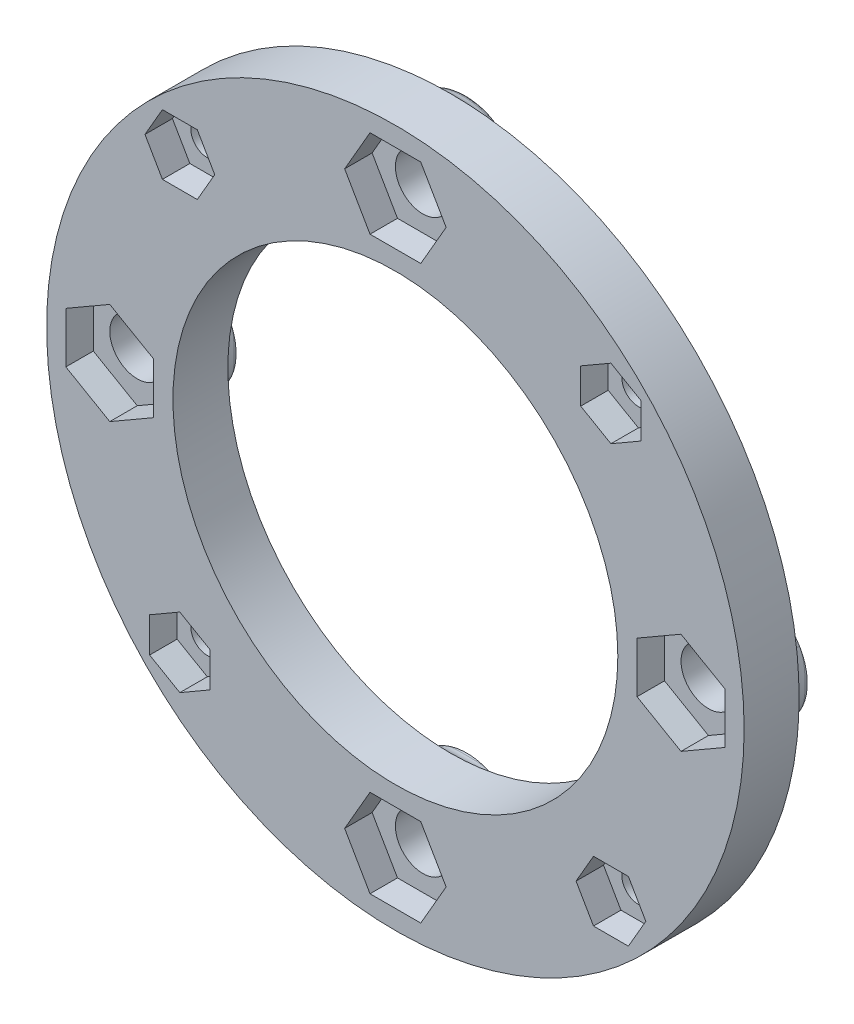
SolidWorks part; units mm, degrees
material "PLA"
ref_plane "Front Plane" through (0, 0, 0) normal (0, 0, 1) x (1, 0, 0)
ref_plane "Top Plane" through (0, 0, 0) normal (0, 1, 0) x (1, 0, 0)
ref_plane "Right Plane" through (0, 0, 0) normal (1, 0, 0) x (0, 0, -1)
sketch "Sketch2" plane through (0, 0, 0) normal (0, 0, 1) x (1, 0, 0)
  line L0 (0, 26) -> (0, 0) construction
  line L1 (0, 0) -> (19.6222, 19.6222) construction
  circle A0 centre (0, 0) radius 31.75
  circle A2 centre (0, 0) radius 26 construction
  circle A3 centre (0, 26) radius 2.5
  circle A4 centre (0, 0) radius 27.75 construction
  circle A5 centre (26, 0) radius 2.5
  circle A8 centre (19.6222, 19.6222) radius 1.5
  circle A9 centre (19.6222, -19.6222) radius 1.5
  circle A11 centre (0, 0) radius 14 construction
  circle A14 centre (0, 26) radius 4.25 construction
  circle A15 centre (0, 0) radius 21.75 construction
  circle A16 centre (0, -26) radius 2.5
  circle A19 centre (-19.6222, -19.6222) radius 1.5
  circle A20 centre (0, 0) radius 30.25 construction
  circle A23 centre (0, 0) radius 20.25
  circle A31 centre (-26, 0) radius 2.5
  circle A33 centre (-19.6222, 19.6222) radius 1.5
  point P17 (0, 0)
  point P24 (0, 0)
  dimension "D2" = 52
  dimension "D4" = 5
  dimension "D7" = 3
  dimension "D3" = 28
  dimension "D10" = 8.5
  dimension "D5" = 4
  dimension "D11" = 45
  dimension "D12" = 1.5
  dimension "D9" = 1.5
  dimension "D6" = 4
  dimension "D8" = 4
extrude "Boss-Extrude1" add sketch "Sketch2" along normal blind 5
sketch "Sketch3" plane through (0, 0, 5) normal (0, 0, 1) x (1, 0, 0)
  line L0 (0, 26) -> (0, 0) construction
  line L13 (-4.6188, 26) -> (-2.3094, 22)
  line L14 (-2.3094, 22) -> (2.3094, 22)
  line L15 (2.3094, 22) -> (4.6188, 26)
  line L16 (4.6188, 26) -> (2.3094, 30)
  line L17 (2.3094, 30) -> (-2.3094, 30)
  line L18 (-2.3094, 30) -> (-4.6188, 26)
  line L20 (19.6222, 16.4468) -> (22.3722, 18.0345)
  line L21 (22.3722, 18.0345) -> (22.3722, 21.2099)
  line L22 (22.3722, 21.2099) -> (19.6222, 22.7976)
  line L23 (19.6222, 22.7976) -> (16.8722, 21.2099)
  line L24 (16.8722, 21.2099) -> (16.8722, 18.0345)
  line L25 (16.8722, 18.0345) -> (19.6222, 16.4468)
  circle A0 centre (0, 26) radius 4 construction
  circle A1 centre (19.6222, 19.6222) radius 2.75 construction
  dimension "D1" = 8
  dimension "D2" = 5.5
extrude "Cut-Extrude1" cut sketch "Sketch3" against normal blind 2.5
pattern_circular "CirPattern1" count 4 over 360 about axis through (0, 0, 5) along (0, 0, -1) of "Cut-Extrude1" reverse direction yes
sketch "Sketch4" plane through (0, 0, 0) normal (0, 0, -1) x (-1, 0, 0)
  circle A0 centre (0, 26) radius 4
  circle A1 centre (0, 26) radius 5
  dimension "D1" = 8
extrude "Boss-Extrude2" add sketch "Sketch4" along normal blind 1.5
fillet "Fillet1" radius 1.5 1 edges at (5, 26, 0)
fillet "Fillet2" radius 0.5 4 edges at (0, 31, -1.5) (0, 21, -1.5) (4.9914, 25.7067, -1.5) (-4.9914, 25.7067, -1.5)
chamfer "Chamfer1" distance 0.25 angle 45 1 edges at (-4, 26, -1.5)
pattern_circular "CirPattern2" count 4 over 360 about axis through (0, 0, 5) along (0, 0, -1) of "Fillet1", "Boss-Extrude2", "Chamfer1" reverse direction yes
equation "\"module\" = 0.5"
equation "\"pressure_angle\" = 20.0"
equation "\"h_a\" = 0.5"
equation "\"h_f\" = 0.625"
equation "\"clr_tip_root\" = 0.125"
equation "\"bearing_ID\" = 60"
equation "\"bearing_OD\" = 78"
equation "\"bearing_height\" = 10"
equation "\"clearance_planet\" = 1.5"
equation "\"case_dist\" = 6.5"
equation "\"Motor_case_OD_max\" = 111.3"
equation "\"case_mounting_PCD\" = 103.8"
equation "\"bearing mount thickness\" = 8"
equation "\"case_mounting_hole_dia\" = 3"
equation "\"output_mounting_PCD\" = 86"
equation "\"output_mounting_hole_dia\" = 4"
equation "\"clearance_case_mount_holes_shell_thickness\" = 1"
equation "\"motor_case_OD_base\" = 101.8"
equation "\"sec_carrier_thickness\" = 5"
equation "\"sun_coupler_hub_thickness\" = 4"
equation "\"clearance_sun_coupler_sec_carrier\" = 1.5"
equation "\"clearance_motor_and_case\" = 5"
equation "\"motor_OD\" = 86.8"
equation "\"Motor_case_thickness\" = 2.5"
equation "\"Motor_case_ID\" = 96.8"
equation "\"case_mounting_hole_shift\" = 1.0"
equation "\"output_mounting_nut_wrench_size\" = 7"
equation "\"output_mounting_nut_thickness\" = 3.2"
equation "\"case_mounting_hole_allen_socket_dia\" = 5.5"
equation "\"output_mounting_nut_depth\" = 3"
equation "\"case_mounting_bolt_depth\" = 4.5"
equation "\"Ns\" = 56"
equation "\"Np_b\" = 48"
equation "\"ring_radial_thickness\" = 5"
equation "\"ring_to_chamfer_clearance\" = 1.5"
equation "\"Motor_case_OD_base_to_chamfer\" = 5"
equation "\"pattern_offset_from_motor_case_OD_base\" = 3"
equation "\"pattern_bulge_dia\" = 3"
equation "\"pattern_num_bulge\" = 18"
equation "\"pattern_depth\" = 2"
equation "\"motor_height\" = 26.5"
equation "\"case_mounting_wrench_size\" = 5.5"
equation "\"case_mounting_nut_clearance\" = 2"
equation "\"base_plate_thickness\" = 4"
equation "\"case_mounting_nut_thickness\" = 2.4"
equation "\"case_mounting_surface_height\" = 4"
equation "\"motor_mount_hole_PCD\" = 32"
equation "\"motor_mount_hole_dia\" = 4"
equation "\"motor_mount_hole_num\" = 4"
equation "\"central_hole_offset_from_motor_mount_PCD\" = 5"
equation "\"wire_slot_dist_from_center\" = 38"
equation "\"wire_slot_length\" = 10"
equation "\"wire_slot_radius\" = 2.5"
equation "\"driver_upper_holes_dist_from_center\" = 29"
equation "\"driver_lower_holes_dist_from_center\" = 13"
equation "\"driver_side_holes_dist_from_center\" = 22.5"
equation "\"driver_mount_holes_dia\" = 3"
equation "\"driver_mount_inserts_OD\" = 4.8"
equation "\"driver_mount_thickness\" = 1.5"
equation "\"driver_mount_height\" = 6"
equation "\"air_flow_hole_offset\" = 3"
equation "\"num_planet\" = 4"
equation "\"planet_pin_bolt_dia\" = 5"
equation "\"planet_pin_socket_head_dia\" = 8.5"
equation "\"carrier_PCD\" = 52.0"
equation "\"D2@Sketch2\"=\"carrier_PCD\""
equation "\"D4@Sketch2\"=\"planet_pin_bolt_dia\""
equation "\"D6@Sketch2\"=\"num_planet\""
equation "\"D8@Sketch2\"=\"num_planet\""
equation "\"D1@CirPattern1\"=\"num_planet\""
equation "\"planet_shaft_dia\" = 8"
equation "\"planet_shaft_step_offset\" = 1"
equation "\"carrier_trapezoidal_support_sun_offset\" = 5"
equation "\"carrier_trapezoidal_support_hole_PCD_offset_bearing_ID\" = 4"
equation "\"carrier_trapezoidal_support_hole_dia\" = 3"
equation "\"carrier_trapezoidal_support_hole_socket_head_dia\" = 5.5"
equation "\"carrier_bearing_step_width\" = 1.5"
equation "\"standard_clearance_1_5mm\" = 1.5"
equation "\"standard_fillet_1_5mm\" = 1.5"
equation "\"sun_shaft_bearing_OD\" = 16"
equation "\"sun_shaft_bearing_width\" = 5"
equation "\"standard_bearing_insertion_chamfer\" = 0.5"
equation "\"D7@Sketch2\"=\"carrier_trapezoidal_support_hole_dia\""
equation "\"D3@Sketch2\"=\"Ns\"*\"module\""
equation "\"carrier_trapezoidal_support_hole_wrench_size\" = 5.5"
equation "\"planet_pin_bolt_wrench_size\" = 8"
equation "\"D1@Boss-Extrude1\"=\"sec_carrier_thickness\""
equation "\"D1@Cut-Extrude1\"=\"sec_carrier_thickness\"/2"
equation "\"D1@Sketch4\"=\"planet_shaft_dia\""
equation "\"D2@Sketch4\"=\"planet_shaft_step_offset\""
equation "\"D1@Boss-Extrude2\"=\"clearance_planet\""
equation "\"D1@Fillet1\"=\"standard_fillet_1_5mm\""
equation "\"D1@Chamfer1\"=\"standard_bearing_insertion_chamfer\"/2"
equation "\"D1@Fillet2\"=\"standard_fillet_1_5mm\"/3"
equation "\"D1@CirPattern2\"=\"num_planet\""
equation "\"D10@Sketch2\"= \"planet_pin_socket_head_dia\""
equation "\"D1@Sketch3\"=\"planet_pin_bolt_wrench_size\""
equation "\"D11@Sketch2\"=180/\"num_planet\""
equation "\"D2@Sketch3\"=\"carrier_trapezoidal_support_hole_wrench_size\""
equation "\"pressure angle\" = 20.0"
equation "\"h_b\" = 0.625"
equation "\"dp_s\" = 28.0"
equation "\"db_s\" = 26.311393382005434"
equation "\"fw_s_calc\" = 2.7970255760332914"
equation "\"alpha_s\" = 0.8539582918412485"
equation "\"beta_s\" = 1.5063691306032174"
equation "\"dp_p_b\" = 24.0"
equation "\"db_p_b\" = 22.552622898861802"
equation "\"fw_p_s\" = 15.90536252346366"
equation "\"alpha_p_b\" = 0.8539582918412414"
equation "\"beta_p_b\" = 2.042083416317517"
equation "\"planet_bearing_OD\" = 12"
equation "\"planet_bearing_width\" = 3.5"
equation "\"planet_bore\" = 10"
equation "\"motor_output_hole_PCD\" = 23"
equation "\"motor_output_hole_dia\" = 4"
equation "\"motor_output_hole_num\" = 4"
equation "\"sun_shaft_bearing_ID\" = 8"
equation "\"sun_hub_dia\" = 30.0"
equation "\"sun_central_bolt_dia\" = 5"
equation "\"sun_central_bolt_socket_head_dia\" = 8.5"
equation "\"fw_s_used\" = 33.32338113475014"
equation "\"motor_output_hole_CSK_OD\" = 8"
equation "\"motor_output_hole_CSK_head_height\" = 2.0"
equation "\"bearing_retainer_thickness\" = 2"
equation "\"Np_s\" = 28"
equation "\"fw_p_b\" = 9.918018611286483"
equation "\"dp_p_s\" = 14.0"
equation "\"db_p_s\" = 13.155696691002717"
equation "\"alpha_p_s\" = 0.8539582918412485"
equation "\"beta_p_s\" = 4.720654844888932"
equation "\"Nr_b\" = 152"
equation "\"dp_r_b\" = 76.0"
equation "\"db_r_b\" = 71.41663917972905"
equation "\"fw_r_b\" = 9.918018611286483"
equation "\"alpha_r_b\" = 0.8539582918412236"
equation "\"beta_r_b\" = 2.8921271099982366"
equation "\"ring_OD_b\" = 86.0"
equation "\"Fillet10\"= IIF ( \"ring_OD_b\" > ( \"bearing_OD\" + 2 * \"bearing mount thickness\" ) , \"suppressed\" , \"unsuppressed\" )"
equation "\"Fillet11\"= IIF ( \"ring_OD_b\" < ( \"bearing_OD\" + 2 * \"bearing mount thickness\" ) , \"suppressed\" , \"unsuppressed\" )"
equation "\"Nr_s\" = 132"
equation "\"clr_tip_root_s\" = 0.125"
equation "\"dp_r_s\" = 66.0"
equation "\"db_r_s\" = 62.01971297186996"
equation "\"fw_r_s\" = 14.40536252346366"
equation "\"alpha_r_s\" = 0.8539582918412449"
equation "\"beta_r_s\" = 3.071552947318853"
equation "\"D9@Sketch2\"=\"standard_clearance_1_5mm\""
equation "\"small_ring_case_thickness\" = 4"
equation "\"carrier_thickness\" = 4"
equation "\"small_ring_output_wall_thickness\" = 5"
equation "\"small_ring_output_wall_to_bearing_shaft_attachement_hole_dia\" = 4"
equation "\"small_ring_output_wall_to_bearing_shaft_attachement_hole_depth\" = 6.5"
equation "\"small_ring_output_wall_to_bearing_shaft_attachement_nut_wrench\" = 7"
equation "\"small_ring_output_wall_to_bearing_shaft_attachement_nut_thickness\" = 3.2"
equation "\"small_ring_output_wall_to_bearing_shaft_attachement_hole_pcd\" = 12"
equation "\"small_ring_output_wall_to_bearing_shaft_attachement_hole_num\" = 3"
equation "\"small_ring_output_wall_to_bearing_shaft_attachement_hole_CSK_OD\" = 8"
equation "\"small_ring_output_wall_to_bearing_shaft_attachement_hole_CSK_head_height\" = 2.0"
equation "\"carrier_small_ring_inner_bearing_ID\" = 20"
equation "\"carrier_small_ring_inner_bearing_OD\" = 32"
equation "\"carrier_small_ring_inner_bearing_height\" = 7"
equation "\"carrier_small_ring_inner_bearing_flap\" = 2"
